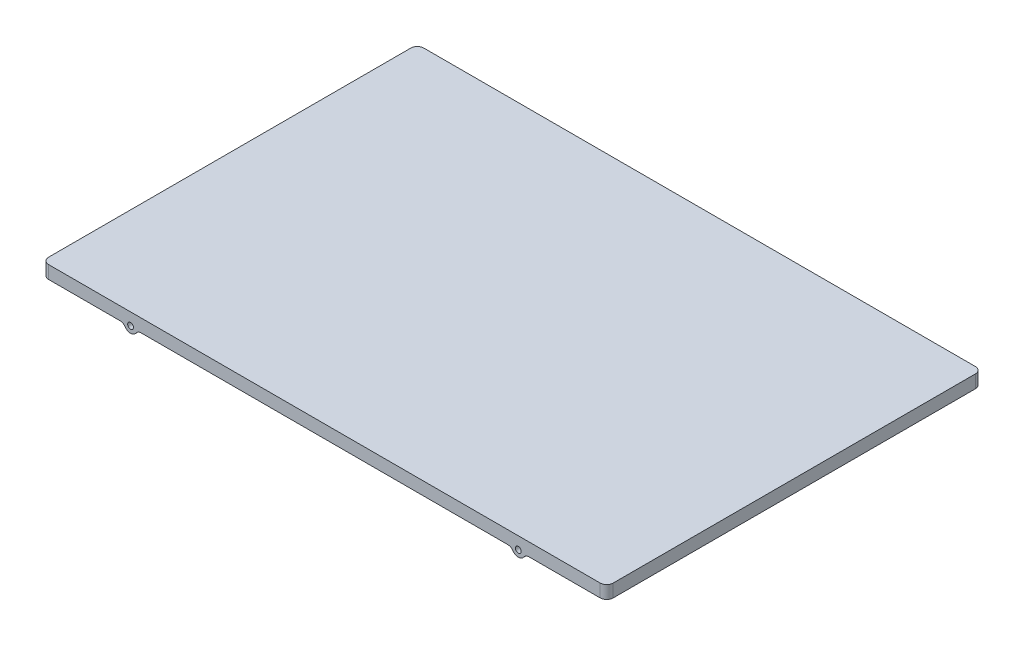
SolidWorks part; units mm, degrees
ref_plane "Front Plane" through (0, 0, 0) normal (0, 0, 1) x (1, 0, 0)
ref_plane "Top Plane" through (0, 0, 0) normal (0, 1, 0) x (1, 0, 0)
ref_plane "Right Plane" through (0, 0, 0) normal (1, 0, 0) x (0, 0, -1)
sketch "Sketch3" plane through (0, 0, 0) normal (0, 1, 0) x (1, 0, 0)
  line L1 (-87.3375, 58.0375) -> (87.3375, 58.0375)
  line L2 (-87.3375, 58.0375) -> (-87.3375, -58.0375)
  line L3 (-87.3375, -58.0375) -> (87.3375, -58.0375)
  line L4 (87.3375, 58.0375) -> (87.3375, -58.0375)
  line L5 (-87.3375, 58.0375) -> (87.3375, -58.0375) construction
  line L6 (-87.3375, -58.0375) -> (87.3375, 58.0375) construction
  point P0 (0, 0)
  dimension "D1" = 116.075
  dimension "D2" = 174.675
extrude "Boss-Extrude1" add sketch "Sketch3" along normal blind 4
fillet "Fillet1" radius 2 4 edges at (87.3375, 2, -58.0375) (87.3375, 2, 58.0375) (-87.3375, 2, 58.0375) (-87.3375, 2, -58.0375)
sketch "Sketch4" plane through (0, 0, 0) normal (0, 1, 0) x (1, 0, 0)
  line L0 (-87.3375, 56.0375) -> (-87.3375, -56.0375) construction
  line L1 (-87.3375, 41.2375) -> (-36.275, 41.2375)
  line L2 (-87.3375, 41.2375) -> (-87.3375, 13.2375)
  line L3 (-87.3375, 13.2375) -> (-36.275, 13.2375)
  line L4 (-35.2125, 40.175) -> (-35.2125, 14.3)
  line L5 (85.3375, 58.0375) -> (-85.3375, 58.0375) construction
  arc A1 (-36.275, 13.2375) -> (-35.2125, 14.3) centre (-36.275, 14.3) ccw
  arc A2 (-36.275, 41.2375) -> (-35.2125, 40.175) centre (-36.275, 40.175) cw
  point P0 (-87.5284, 41.3)
  point P6 (0, 0)
  point P7 (0, 0)
  point P12 (-87.3375, 13.2375)
  point P15 (-35.2125, 13.2375)
  point P20 (-87.3375, 41.2375)
  dimension "D1" = 16.8
  dimension "D2" = 52.125
  dimension "D3" = 28
extrude "Cut-Extrude1" cut sketch "Sketch4" along normal blind 2
sketch "Sketch5" plane through (0, 0, 58.0375) normal (0, 0, 1) x (1, 0, 0)
  line L0 (-85.3375, 4) -> (85.3375, 4) construction
  circle A0 centre (60, 0.25) radius 0.9
  circle A1 centre (60, 0.25) radius 2
  line M3 (-85.3375, 0) -> (85.3375, 0)
  dimension "D2" = 1.8
  dimension "D3" = 4
  dimension "D1" = 3.75
  dimension "D4" = 60
extrude "Boss-Extrude2" add sketch "Sketch5" against normal blind 9
fillet "Fillet2" radius 2 1 edges at (58.5756, 0, 49.0375)
extrude "Cut-Extrude2" cut sketch "Sketch5<6>" against normal blind 11 contours A0 M3 region at (60, 0.501, 58.0375)
sketch "Sketch5<6>" plane through (0, 0, 58.0375) normal (0, 0, 1) x (1, 0, 0) same geometry as "Sketch5"
fillet "Fillet3" radius 2 2 edges at (61.9843, 0, 52.5375) (58.0157, 0, 52.5375)
ref_plane "Plane1" through (0, 0, 0) normal (1, 0, 0) x (0, 0, -1)
mirror "Mirror1" about plane through (0, 0, 0) normal (1, 0, 0) of "Fillet3", "Cut-Extrude2", "Fillet2", "Boss-Extrude2"
